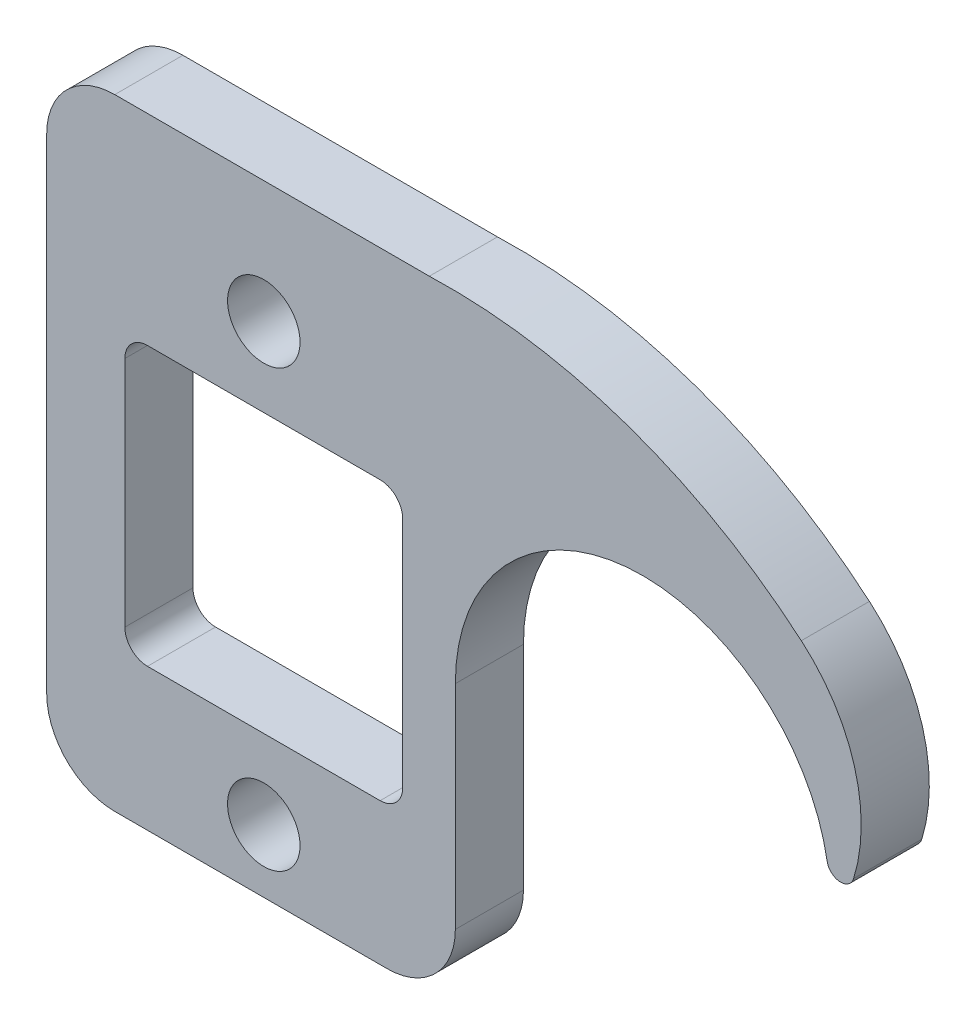
SolidWorks part; units mm, degrees
ref_plane "Front Plane" through (0, 0, 0) normal (0, 0, 1) x (1, 0, 0)
ref_plane "Top Plane" through (0, 0, 0) normal (0, 1, 0) x (1, 0, 0)
ref_plane "Right Plane" through (0, 0, 0) normal (1, 0, 0) x (0, 0, -1)
sketch "Sketch1" plane through (0, 0, 0) normal (0, 0, 1) x (1, 0, 0)
  line L0 (-22.225, -12.7) -> (-22.225, 13.4937) construction
  line L1 (-47.625, -12.7) -> (-22.225, -12.7) construction
  line L2 (-47.625, -12.7) -> (-47.625, 12.7) construction
  line L3 (-47.625, 12.7) -> (-22.225, 12.7) construction
  line L4 (-22.225, -12.7) -> (-22.225, 12.7) construction
  line L5 (-47.625, -12.7) -> (-22.225, 12.7) construction
  line L6 (-47.625, 12.7) -> (-22.225, -12.7) construction
  line L7 (-48.4636, -19.8438) -> (-48.4636, -13.4937)
  line L8 (-46.6725, 13.4937) -> (-22.225, 13.4937)
  line L9 (-49.2125, 19.05) -> (-10.7582, 19.05)
  line L10 (-10.7582, 19.05) -> (-0.6577, 22.5212)
  line L11 (-48.4636, -19.8438) -> (-21.385, -19.8438)
  line L12 (-49.2125, 10.9537) -> (-49.2125, 5.5562)
  line L13 (-49.2125, 5.5562) -> (-55.5625, 5.5562)
  line L14 (-55.5625, 5.5562) -> (-55.5625, 12.7)
  line L15 (-22.225, -12.7) -> (-22.225, 13.4937) construction
  line L16 (-48.4636, -13.4937) -> (-21.4313, -13.4937)
  line L17 (-21.4313, -13.4937) -> (-21.4313, 13.4937)
  line L19 (-22.225, 13.4937) -> (-21.4313, 13.4937)
  circle A0 centre (0, 0) radius 15.875 construction
  arc A1 (17.2058, 2.9834) -> (-15.0686, -8.8248) centre (0, 0) ccw
  arc A2 (19.6706, 2.8257) -> (-0.6577, 22.5212) centre (4.5018, 7.5081) ccw
  arc A3 (-21.385, -19.8438) -> (-15.0686, -8.8248) centre (-21.385, -12.5239) ccw
  arc A4 (-55.5625, 12.7) -> (-49.2125, 19.05) centre (-49.2125, 12.7) cw
  arc A5 (-46.6725, 13.4937) -> (-49.2125, 10.9537) centre (-46.6725, 10.9537) ccw
  arc A6 (19.6706, 2.8257) -> (17.2058, 2.9834) centre (18.4571, 3.2003) cw
  point P3 (-34.925, 0)
  point P11 (4.5018, 23.3831)
  point P24 (-49.2125, 13.4937)
  dimension "D1" = 31.75
  dimension "D5" = 1.5875
  dimension "D6" = 31.75
  dimension "D11" = 7.3199
  dimension "D15" = 6.35
  dimension "D18" = 2.54
  dimension "D22" = 1.27
  dimension "D2" = 6.35
  dimension "D3" = 25.4
  dimension "D4" = 6.35
  dimension "D7" = 6.35
  dimension "D8" = 10.6803
  dimension "D9" = 0.7937
  dimension "D10" = 1.5875
  dimension "D12" = 6.35
  dimension "D13" = 7.9375
  dimension "D14" = 19.05
  dimension "D16" = 4.5018
  dimension "D17" = 1.5875
  dimension "D19" = 0.7937
  dimension "D20" = 13.4937
  dimension "D21" = 48.4636
extrude "Boss-Extrude1" add sketch "Sketch1" along normal mid plane 6.35 contours A4 L14 L13 L12 L8 L0 L11 A3 A1 A2 L10 L9 region at (-20.7804, 5.2798, 0)
fillet "Fillet1" radius 12.7 1 edges at (-10.7582, 19.05, 0)
sketch "Sketch2" plane through (0, 0, 0) normal (0, 0, 1) x (1, 0, 0)
  line L0 (-55.5625, 12.7) -> (-55.5625, -26.1938)
  line L2 (-48.4636, -19.8438) -> (-21.385, -19.8438) construction
  line L3 (-49.2125, -13.4937) -> (-49.2125, 10.9537)
  line L4 (-49.2125, -13.4937) -> (-21.4313, -13.4937)
  line L5 (-21.4313, -13.4937) -> (-21.4313, 13.4937)
  line L6 (-21.4313, 13.4937) -> (-46.6725, 13.4937)
  line L7 (-46.6725, 13.4937) -> (-21.4313, 13.4937) construction
  line L8 (-55.5625, -26.1938) -> (-21.4313, -26.1938)
  line L9 (-21.4313, -13.4937) -> (-17.4625, 0)
  arc A0 (-53.6516, 17.2406) -> (14.7931, 19.5955) centre (-18.1389, -19.0842) cw
  arc A3 (-49.2125, 19.05) -> (-55.5625, 12.7) centre (-49.2125, 12.7) ccw construction
  arc A4 (19.6706, 2.8257) -> (-0.6577, 22.5212) centre (4.5018, 7.5081) ccw construction
  arc A5 (-49.2125, 19.05) -> (-55.5625, 12.7) centre (-49.2125, 12.7) ccw
  arc A6 (-21.4313, -26.1938) -> (-17.4625, 0) centre (-106.3625, 0.0722) ccw
  arc A7 (-46.6725, 13.4937) -> (-49.2125, 10.9537) centre (-46.6725, 10.9537) ccw construction
  arc A8 (-49.2125, 10.9537) -> (-46.6725, 13.4937) centre (-46.6725, 10.9537) cw
  arc A9 (-21.4313, 13.4937) -> (14.7931, 19.5955) centre (6.7531, -43.2511) cw
  arc A10 (17.2058, 2.9834) -> (-15.0686, -8.8248) centre (0, 0) ccw construction
  dimension "D1" = 50.8
  dimension "D2" = 6.35
  dimension "D3" = 88.9
extrude "Boss-Extrude2" add sketch "Sketch2" along normal up to surface (3.175 mm away) and the other way up to surface (3.175 mm away) contours L6 A9 A0 A5 L0 L4 L3 A8 region at (-54.2254, 14.8097, 0) up to face at (-27.4588, 5.697, 3.175) other way up to face at (-27.4588, 5.697, -3.175)
sketch "Sketch3" plane through (0, 0, 3.175) normal (0, 0, 1) x (1, 0, 0)
  line L0 (-49.2125, -13.4937) -> (-21.4313, -13.4937) construction
  line L1 (-21.4313, -13.4937) -> (-21.4313, 13.4937) construction
  circle A2 centre (-35.3219, 0) radius 1.9045
  point P7 (-35.3219, -13.4937)
  point P10 (-21.4313, 0)
fillet "Fillet2" radius 2.54 3 edges at (-49.2125, -13.4937, 0) (-21.4313, -13.4937, 0) (-21.4313, 13.4937, 0)
sketch "Sketch4" plane through (0, 0, 0) normal (0, 0, 1) x (1, 0, 0)
  line L1 (-46.7519, -13.97) -> (-23.8919, -13.97)
  line L2 (-49.2919, -11.43) -> (-49.2919, 11.43)
  line L3 (-46.7519, 13.97) -> (-23.8919, 13.97)
  line L4 (-21.3519, -11.43) -> (-21.3519, 11.43)
  line L5 (-49.2919, -13.97) -> (-21.3519, 13.97) construction
  line L6 (-49.2919, 13.97) -> (-21.3519, -13.97) construction
  arc A0 (-49.2919, 11.43) -> (-46.7519, 13.97) centre (-46.7519, 11.43) cw
  arc A1 (-23.8919, 13.97) -> (-21.3519, 11.43) centre (-23.8919, 11.43) cw
  arc A2 (-23.8919, -13.97) -> (-21.3519, -11.43) centre (-23.8919, -11.43) ccw
  arc A3 (-46.7519, -13.97) -> (-49.2919, -11.43) centre (-46.7519, -11.43) cw
  point P0 (-35.3219, 0)
  dimension "D3" = 2.54
  dimension "D1" = 27.94
  dimension "D2" = 27.94
extrude "Cut-Extrude1" cut sketch "Sketch4" against normal through all both and the other way through all
sketch "Sketch6" plane through (0, 0, 0) normal (0, 0, 1) x (1, 0, 0)
  line L1 (-51.959, -15.0546) -> (-26.559, -15.0546)
  line L2 (-51.959, -15.0546) -> (-51.959, 10.3454)
  line L3 (-51.959, 10.3454) -> (-26.559, 10.3454)
  line L4 (-26.559, -15.0546) -> (-26.559, 10.3454)
  line L5 (-51.959, -15.0546) -> (-26.559, 10.3454) construction
  line L6 (-51.959, 10.3454) -> (-26.559, -15.0546) construction
  point P0 (-39.259, -2.3546)
  dimension "D1" = 25.4
  dimension "D2" = 25.4
sketch "Sketch5" plane through (0, 0, 3.175) normal (0, 0, 1) x (1, 0, 0)
  line L0 (-23.8919, 13.97) -> (-46.7519, 13.97) construction
  line L2 (-49.2919, 0) -> (-21.3519, 0) construction
  line L3 (-49.2919, 11.43) -> (-49.2919, -11.43) construction
  line L4 (-21.3519, -11.43) -> (-21.3519, 11.43) construction
  circle A0 centre (-35.3219, 20.32) radius 3.3782
  circle A2 centre (-35.3219, -20.32) radius 3.3782
  point P3 (-35.3219, 13.97)
  dimension "D1" = 6.7564
  dimension "D2" = 6.35
extrude "Cut-Extrude2" cut sketch "Sketch5" against normal through all both and the other way through all
sketch "Sketch7" plane through (0, 0, 0) normal (0, 0, 1) x (1, 0, 0)
  line L0 (-17.4625, 0) -> (-2.6524, -16.1841)
  line L1 (-2.6524, -16.1841) -> (-21.4313, -26.1938)
  arc A0 (-21.4313, -26.1938) -> (-17.4625, 0) centre (-106.3625, 0.0722) ccw
  arc A1 (17.2058, 2.9834) -> (-15.0686, -8.8248) centre (0, 0) ccw construction
  dimension "D1" = 88.9
extrude "Cut-Extrude3" cut sketch "Sketch7" against normal through all both and the other way through all
fillet "Fillet3" radius 6.35 2 edges at (-55.5625, -26.1938, 0) (-21.4313, -26.1938, 0)
sketch "Sketch8" plane through (0, 0, 0) normal (0, 0, 1) x (1, 0, 0)
  line L1 (-51.1058, -15.2652) -> (-19.5379, -15.2652)
  line L2 (-51.1058, -15.2652) -> (-51.1058, 15.2652)
  line L3 (-51.1058, 15.2652) -> (-19.5379, 15.2652)
  line L4 (-19.5379, -15.2652) -> (-19.5379, 15.2652)
  line L5 (-51.1058, -15.2652) -> (-19.5379, 15.2652) construction
  line L6 (-51.1058, 15.2652) -> (-19.5379, -15.2652) construction
  point P0 (-35.3219, 0)
extrude "Boss-Extrude3" add sketch "Sketch8" along normal up to surface (3.175 mm away) and the other way up to surface (3.175 mm away) up to face at (-22.5789, -1.1592, 3.175) other way up to face at (-31.9437, 20.32, -3.175)
sketch "Sketch10" plane through (0, 0, 3.175) normal (0, 0, 1) x (1, 0, 0)
  line L0 (-94.7255, 36.0571) -> (-94.7255, 39.2744) construction
  line L1 (-94.7255, 40.2904) -> (-94.7255, 41.2641) construction
  line L2 (-96.9353, 41.2641) -> (-96.9353, 39.1327) construction
  line L3 (-98.6697, 38.4143) -> (-101.9997, 41.7443) construction
  line L4 (-102.9297, 43.9894) -> (-102.9297, 47.2256) construction
  line L5 (-101.9997, 49.4706) -> (-98.6697, 52.8007) construction
  line L6 (-96.9353, 52.0823) -> (-96.9353, 49.9509) construction
  line L7 (-94.7255, 49.9509) -> (-94.7255, 50.9245) construction
  line L8 (-94.7255, 51.9405) -> (-94.7255, 55.1579) construction
  line L9 (-97.8751, 58.3075) -> (-101.0924, 58.3075) construction
  line L10 (-102.1084, 58.3075) -> (-103.0821, 58.3075) construction
  line L11 (-103.0821, 56.0977) -> (-100.9507, 56.0977) construction
  line L12 (-100.2323, 54.3632) -> (-103.5623, 51.0332) construction
  line L13 (-105.8074, 50.1033) -> (-109.0436, 50.1033) construction
  line L14 (-111.2887, 51.0332) -> (-114.6187, 54.3632) construction
  line L15 (-113.9003, 56.0977) -> (-111.7689, 56.0977) construction
  line L16 (-111.7689, 58.3075) -> (-112.7426, 58.3075) construction
  line L17 (-113.7586, 58.3075) -> (-116.9759, 58.3075) construction
  line L18 (-120.1255, 55.1579) -> (-120.1255, 51.9405) construction
  line L19 (-120.1255, 50.9245) -> (-120.1255, 49.9509) construction
  line L20 (-117.9157, 49.9509) -> (-117.9157, 52.0823) construction
  line L21 (-116.1813, 52.8007) -> (-112.8512, 49.4706) construction
  line L22 (-111.9213, 47.2256) -> (-111.9213, 43.9894) construction
  line L23 (-112.8512, 41.7443) -> (-116.1813, 38.4143) construction
  line L24 (-117.9157, 39.1327) -> (-117.9157, 41.2641) construction
  line L25 (-120.1255, 41.2641) -> (-120.1255, 40.2904) construction
  line L26 (-120.1255, 39.2744) -> (-120.1255, 36.0571) construction
  line L27 (-116.9759, 32.9075) -> (-113.7586, 32.9075) construction
  line L28 (-112.7426, 32.9075) -> (-111.7689, 32.9075) construction
  line L29 (-111.7689, 35.1173) -> (-113.9003, 35.1173) construction
  line L30 (-114.6187, 36.8517) -> (-111.2887, 40.1817) construction
  line L31 (-109.0436, 41.1117) -> (-105.8074, 41.1117) construction
  line L32 (-103.5623, 40.1817) -> (-100.2323, 36.8517) construction
  line L33 (-100.9507, 35.1173) -> (-103.0821, 35.1173) construction
  line L34 (-103.0821, 32.9075) -> (-102.1084, 32.9075) construction
  line L35 (-101.0924, 32.9075) -> (-97.8751, 32.9075) construction
  line L39 (-46.1677, -12.954) -> (-24.4761, -12.954)
  line L40 (-48.2759, -10.8458) -> (-48.2759, 10.8458)
  line L41 (-46.1677, 12.954) -> (-24.4761, 12.954)
  line L42 (-22.3679, -10.8458) -> (-22.3679, 10.8458)
  line L43 (-48.2759, -12.954) -> (-22.3679, 12.954) construction
  line L44 (-48.2759, 12.954) -> (-22.3679, -12.954) construction
  arc A0 (-94.7256, 35.0411) -> (-94.7255, 36.0571) centre (-94.7255, 35.5491) cw construction
  arc A1 (-94.7255, 39.2744) -> (-94.7255, 40.2904) centre (-94.7255, 39.7824) cw construction
  arc A2 (-94.7255, 41.2641) -> (-96.9353, 41.2641) centre (-95.8304, 41.2641) ccw construction
  arc A3 (-96.9353, 39.1327) -> (-98.6697, 38.4143) centre (-97.9513, 39.1327) cw construction
  arc A4 (-101.9997, 41.7443) -> (-102.9297, 43.9894) centre (-99.7547, 43.9894) cw construction
  arc A5 (-102.9297, 47.2256) -> (-101.9997, 49.4706) centre (-99.7547, 47.2256) cw construction
  arc A6 (-98.6697, 52.8007) -> (-96.9353, 52.0823) centre (-97.9513, 52.0823) cw construction
  arc A7 (-96.9353, 49.9509) -> (-94.7255, 49.9509) centre (-95.8304, 49.9509) ccw construction
  arc A8 (-94.7255, 50.9245) -> (-94.7255, 51.9405) centre (-94.7255, 51.4325) cw construction
  arc A9 (-94.7255, 55.1579) -> (-94.7256, 56.1739) centre (-94.7255, 55.6659) cw construction
  arc A10 (-94.7256, 56.1739) -> (-96.8591, 58.3073) centre (-96.8337, 56.1993) ccw construction
  arc A11 (-96.8591, 58.3073) -> (-97.8751, 58.3075) centre (-97.3671, 58.3075) cw construction
  arc A12 (-101.0924, 58.3075) -> (-102.1084, 58.3075) centre (-101.6004, 58.3075) cw construction
  arc A13 (-103.0821, 58.3075) -> (-103.0821, 56.0977) centre (-103.0821, 57.2026) ccw construction
  arc A14 (-100.9507, 56.0977) -> (-100.2323, 54.3632) centre (-100.9507, 55.0817) cw construction
  arc A15 (-103.5623, 51.0332) -> (-105.8074, 50.1033) centre (-105.8074, 53.2783) cw construction
  arc A16 (-109.0436, 50.1033) -> (-111.2887, 51.0332) centre (-109.0436, 53.2783) cw construction
  arc A17 (-114.6187, 54.3632) -> (-113.9003, 56.0977) centre (-113.9003, 55.0817) cw construction
  arc A18 (-111.7689, 56.0977) -> (-111.7689, 58.3075) centre (-111.7689, 57.2026) ccw construction
  arc A19 (-112.7426, 58.3075) -> (-113.7586, 58.3075) centre (-113.2506, 58.3075) cw construction
  arc A20 (-116.9759, 58.3075) -> (-117.9919, 58.3073) centre (-117.4839, 58.3075) cw construction
  arc A21 (-117.9919, 58.3073) -> (-120.1253, 56.1739) centre (-118.0173, 56.1993) ccw construction
  arc A22 (-120.1253, 56.1739) -> (-120.1255, 55.1579) centre (-120.1255, 55.6659) cw construction
  arc A23 (-120.1255, 51.9405) -> (-120.1255, 50.9245) centre (-120.1255, 51.4325) cw construction
  arc A24 (-120.1255, 49.9509) -> (-117.9157, 49.9509) centre (-119.0206, 49.9509) ccw construction
  arc A25 (-117.9157, 52.0823) -> (-116.1813, 52.8007) centre (-116.8997, 52.0823) cw construction
  arc A26 (-112.8512, 49.4706) -> (-111.9213, 47.2256) centre (-115.0963, 47.2256) cw construction
  arc A27 (-111.9213, 43.9894) -> (-112.8512, 41.7443) centre (-115.0963, 43.9894) cw construction
  arc A28 (-116.1813, 38.4143) -> (-117.9157, 39.1327) centre (-116.8997, 39.1327) cw construction
  arc A29 (-117.9157, 41.2641) -> (-120.1255, 41.2641) centre (-119.0206, 41.2641) ccw construction
  arc A30 (-120.1255, 40.2904) -> (-120.1255, 39.2744) centre (-120.1255, 39.7824) cw construction
  arc A31 (-120.1255, 36.0571) -> (-120.1253, 35.0411) centre (-120.1255, 35.5491) cw construction
  arc A32 (-120.1253, 35.0411) -> (-117.9919, 32.9076) centre (-118.0173, 35.0157) ccw construction
  arc A33 (-117.9919, 32.9076) -> (-116.9759, 32.9075) centre (-117.4839, 32.9075) cw construction
  arc A34 (-113.7586, 32.9075) -> (-112.7426, 32.9075) centre (-113.2506, 32.9075) cw construction
  arc A35 (-111.7689, 32.9075) -> (-111.7689, 35.1173) centre (-111.7689, 34.0124) ccw construction
  arc A36 (-113.9003, 35.1173) -> (-114.6187, 36.8517) centre (-113.9003, 36.1333) cw construction
  arc A37 (-111.2887, 40.1817) -> (-109.0436, 41.1117) centre (-109.0436, 37.9367) cw construction
  arc A38 (-105.8074, 41.1117) -> (-103.5623, 40.1817) centre (-105.8074, 37.9367) cw construction
  arc A39 (-100.2323, 36.8517) -> (-100.9507, 35.1173) centre (-100.9507, 36.1333) cw construction
  arc A40 (-103.0821, 35.1173) -> (-103.0821, 32.9075) centre (-103.0821, 34.0124) ccw construction
  arc A41 (-102.1084, 32.9075) -> (-101.0924, 32.9075) centre (-101.6004, 32.9075) cw construction
  arc A42 (-97.8751, 32.9075) -> (-96.8591, 32.9076) centre (-97.3671, 32.9075) cw construction
  arc A43 (-96.8591, 32.9076) -> (-94.7256, 35.0411) centre (-96.8337, 35.0157) ccw construction
  circle A44 centre (-107.4255, 45.6075) radius 2.6035 construction
  arc A45 (-46.1677, -12.954) -> (-48.2759, -10.8458) centre (-46.1677, -10.8458) cw
  arc A46 (-24.4761, -12.954) -> (-22.3679, -10.8458) centre (-24.4761, -10.8458) ccw
  arc A47 (-24.4761, 12.954) -> (-22.3679, 10.8458) centre (-24.4761, 10.8458) cw
  arc A48 (-48.2759, 10.8458) -> (-46.1677, 12.954) centre (-46.1677, 10.8458) cw
  point P127 (-35.3219, 0)
  point P133 (-35.3219, 20.32)
  dimension "D1" = 25.908
  dimension "D2" = 25.908
  dimension "D3" = 2.1082
extrude "Cut-Extrude4" cut sketch "Sketch10" against normal through all both and the other way through all
sketch "Sketch11" plane through (0, 0, 3.175) normal (0, 0, 1) x (1, 0, 0)
  line L0 (-17.4625, 0) -> (-17.4625, -26.1938)
  line L1 (-17.4625, -26.1938) -> (-26.2509, -26.1938)
  line L2 (-26.2509, -26.1938) -> (-17.4625, 0)
extrude "Boss-Extrude4" add sketch "Sketch11" against normal up to surface (6.35 mm away) up to face at (-35.3219, 0, -3.175)
fillet "Fillet4" radius 6.35 1 edges at (-17.4625, -26.1938, 0)
sketch "Sketch12" plane through (0, 0, 0) normal (0, 0, 1) x (1, 0, 0)
  line L0 (-19.8857, 31.6857) -> (-55.5625, 31.6857)
  line L1 (-55.5625, 31.6857) -> (-55.5625, 12.7)
  arc A0 (14.7931, 19.5955) -> (-53.6516, 17.2406) centre (-18.1389, -19.0842) ccw construction
  arc A1 (-55.5625, 12.7) -> (-19.8857, 31.6857) centre (-4.8408, -39.5993) cw
extrude "Boss-Extrude5" add sketch "Sketch12" along normal up to surface (3.175 mm away) and the other way up to surface (3.175 mm away) up to face at (-22.089, -1.0234, 3.175) other way up to face at (-35.3219, 0, -3.175)
fillet "Fillet5" radius 6.35 1 edges at (-55.5625, 31.6857, 0)
